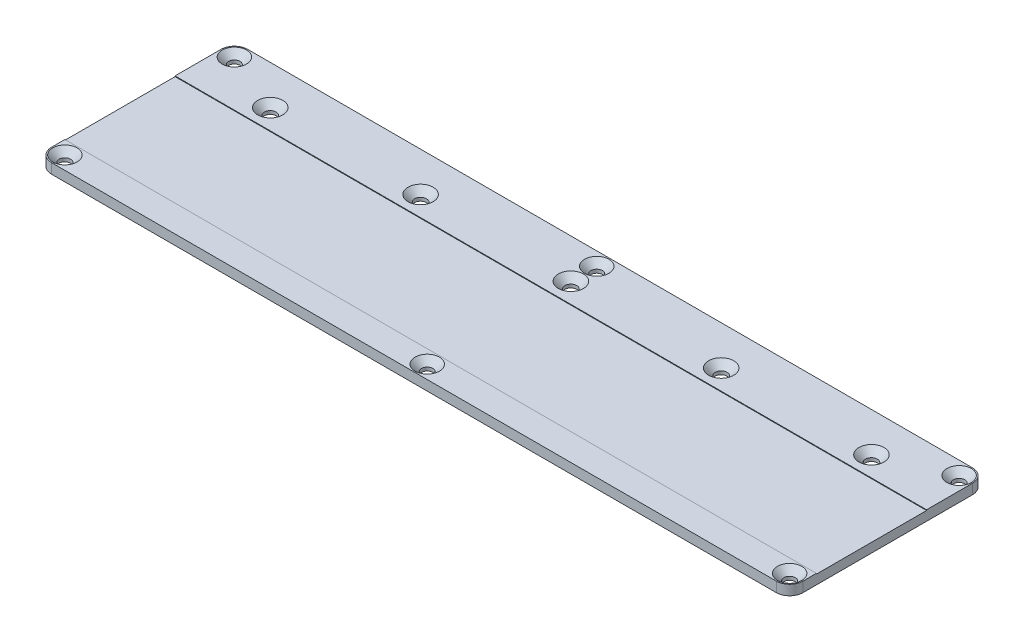
SolidWorks part; units mm, degrees
ref_plane "Front Plane" through (0, 0, 0) normal (0, 0, 1) x (1, 0, 0)
ref_plane "Top Plane" through (0, 0, 0) normal (0, 1, 0) x (1, 0, 0)
ref_plane "Right Plane" through (0, 0, 0) normal (1, 0, 0) x (0, 0, -1)
sketch "Sketch1" plane through (0, 0, 0) normal (0, 1, 0) x (1, 0, 0)
  line L0 (-112.5, 13.625) -> (112.5, 13.625) construction
  line L1 (-112.5, -25.375) -> (112.5, -25.375) construction
  line L2 (-112.5, -25.375) -> (-112.5, 25.375)
  line L3 (-112.5, 25.375) -> (112.5, 25.375)
  line L4 (112.5, -25.375) -> (112.5, 25.375)
  line L5 (-112.5, -25.375) -> (112.5, 25.375) construction
  line L6 (-112.5, 25.375) -> (112.5, -25.375) construction
  line L7 (-112.5, -25.375) -> (112.5, -25.375) construction
  line L8 (-112.5, -25.375) -> (-112.5, 7.625)
  line L9 (-112.5, 7.625) -> (112.5, 7.625) construction
  line L10 (112.5, -25.375) -> (112.5, 7.625)
  line L12 (-112.5, -25.375) -> (112.5, -25.375)
  line L13 (-112.5, -25.375) -> (-112.5, -33.375)
  line L14 (-112.5, -33.375) -> (112.5, -33.375)
  line L15 (112.5, -25.375) -> (112.5, -33.375)
  circle A0 centre (0, 13.625) radius 3.75 construction
  point P0 (0, 0)
  point P10 (0, 7.625)
  dimension "D7" = 7.5
  dimension "D1" = 112.5
  dimension "D3" = 33
  dimension "D4" = 225
  dimension "D5" = 6
  dimension "D6" = 8
  dimension "D2" = 11.75
extrude "Boss-Extrude1" add sketch "Sketch1" along normal blind 3 contours L1 L4 L3 L2 | L13 L12 L15 L14 region at (0, 0, 0)
sketch "Sketch2" plane through (0, 3, 0) normal (0, 1, 0) x (1, 0, 0)
  line L0 (-90, -8.875) -> (-45, -8.875) construction
  line L1 (-45, -8.875) -> (0, -8.875) construction
  line L2 (0, -8.875) -> (45, -8.875) construction
  line L3 (45, -8.875) -> (90, -8.875) construction
  line L4 (112.5, -33.375) -> (112.5, 25.375) construction
  line L6 (-112.5, -25.375) -> (112.5, -25.375)
  line L7 (-112.5, -25.375) -> (-112.5, 7.625)
  line L8 (-112.5, 7.625) -> (112.5, 7.625)
  line L9 (112.5, -25.375) -> (112.5, 7.625)
  line L10 (-112.5, -25.375) -> (112.5, 7.625) construction
  line L11 (-112.5, 7.625) -> (112.5, -25.375) construction
  circle A0 centre (-90, -8.875) radius 15
  circle A1 centre (-45, -8.875) radius 15
  circle A2 centre (0, -8.875) radius 15
  circle A3 centre (45, -8.875) radius 15
  circle A4 centre (90, -8.875) radius 15
  line M11 (112.5, -33.375) -> (112.5, 25.375)
  line M13 (-112.5, 25.375) -> (-112.5, -33.375)
  dimension "D1" = 30
  dimension "D2" = 45
  dimension "D3" = 33
  dimension "D4" = 24.5
sketch "Sketch3" plane through (0, 3, 0) normal (0, 1, 0) x (1, 0, 0)
  line L0 (-90, 13.625) -> (-45, 13.625) construction
  line L1 (-45, 13.625) -> (0, 13.625) construction
  line L2 (0, 13.625) -> (45, 13.625) construction
  line L3 (45, 13.625) -> (90, 13.625) construction
  line L4 (-112.5, 25.375) -> (112.5, 25.375) construction
  line L6 (-1.25, 12.375) -> (1.25, 12.375) construction
  line L7 (-1.25, 12.375) -> (-1.25, 14.875) construction
  line L8 (-1.25, 14.875) -> (1.25, 14.875) construction
  line L9 (1.25, 12.375) -> (1.25, 14.875) construction
  line L10 (-1.25, 12.375) -> (1.25, 14.875) construction
  line L11 (-1.25, 14.875) -> (1.25, 12.375) construction
  circle A0 centre (0, 13.625) radius 1.7678
  circle A1 centre (45, 13.625) radius 1.7678
  circle A2 centre (90, 13.625) radius 1.7678
  circle A3 centre (-45, 13.625) radius 1.7678
  circle A4 centre (-90, 13.625) radius 1.7678
  dimension "D2" = 11.75
  dimension "D1" = 45
  dimension "D3" = 2.5
extrude "Cut-Extrude1" cut sketch "Sketch3" against normal through all
chamfer "Chamfer2" distance 2 angle 45 5 edges at (90, 3, -11.8572) (45, 3, -11.8572) (0, 3, -11.8572) (-45, 3, -11.8572) (-90, 3, -11.8572)
extrude "Cut-Extrude2" cut sketch "Sketch2" against normal blind 0.2 contours L8 L6 A4 A3 A2 A1 A0 M13 M11 | A0 | A1 | A2 | A3 | A4 region at (-110.2259, 3, 8.875) region at (-90, 3, 8.875) region at (-45, 3, 8.875) region at (0, 3, 8.875) region at (45, 3, 8.875) region at (90, 3, 8.875)
fillet "Fillet1" radius 4 4 edges at (-112.5, 1.5, -25.375) (112.5, 1.5, 33.375) (-112.5, 1.5, 33.375) (112.5, 1.5, -25.375)
sketch "Sketch6" plane through (0, 3, 0) normal (0, 1, 0) x (1, 0, 0)
  line L0 (112.5, -25.375) -> (112.5, 7.625) construction
  line L1 (-108.5, 21.375) -> (108.5, 21.375) construction
  line L2 (-108.5, 21.375) -> (-108.5, -29.375) construction
  line L3 (-108.5, -29.375) -> (108.5, -29.375) construction
  line L4 (108.5, 21.375) -> (108.5, -29.375) construction
  line L5 (-112.5, -25.375) -> (-112.5, 7.625) construction
  line L6 (-108.5, -33.375) -> (108.5, -33.375) construction
  line L7 (-108.5, 25.375) -> (108.5, 25.375) construction
  point P12 (0, 21.375)
  point P13 (0, -29.375)
  dimension "D1" = 4
  dimension "D2" = 4
  dimension "D3" = 4
  dimension "D4" = 4
hole_wizard "CSK for M3 Countersunk Flat Head Screw1" positions "Sketch4" profile "Sketch5" countersink size "M3" standard "ISO" end condition through all
sketch "Sketch4" plane through (0, 3, 0) normal (0, 1, 0) x (1, 0, 0)
  point P3 (108.5, 21.375)
  point P6 (108.5, -29.375)
  point P9 (-108.5, -29.375)
  point P12 (-108.5, 21.375)
  point P15 (0, 21.375)
  point P18 (0, -29.375)
sketch "Sketch5" plane through (108.5, 3, -21.375) normal (1, 0, 0) x (0, 0, 1)
  line L0 (0, 0) -> (0, 3)
  line L1 (0, 3) -> (1.7, 3)
  line L2 (1.7, 3) -> (1.7, 1.95)
  line L3 (1.7, 1.95) -> (3.65, 0)
  line L5 (3.65, 0) -> (0, 0)
  line L6 (-1.7, 1.95) -> (-3.65, 0) construction
  line L11 (0, -6.35) -> (0, 107.95) construction
  dimension "Thru Hole Dia." = 3.4
  dimension "Thru Hole Depth" = 3
  dimension "Near C'Sink Dia." = 7.3
  dimension "Near C'Sink Angle" = 90
equation "\"Target White\"= 550mm"
equation "\"Scaled Distance\"= 1.5"
equation "\"Scale Factor\"= 25 / \"Scaled Distance\"'Scaled "
equation "\"Scaled White\"= \"Target White\" / \"Scale Factor\""
equation "\"Scaled Spacing\"= 750 / \"Scale Factor\""
equation "\"D4@Sketch1\"=\"Scaled Spacing\"*5"
equation "\"D1@Sketch3\"=\"Scaled Spacing\""
